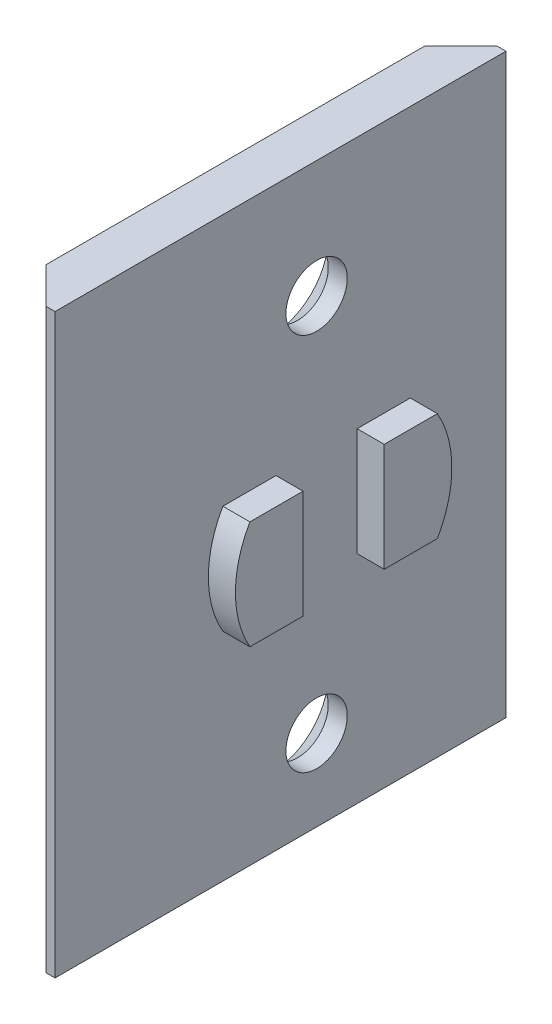
SolidWorks part; units mm, degrees
material "Сталь"
ref_plane "Спереди" through (0, 0, 0) normal (0, 0, 1) x (1, 0, 0)
ref_plane "Сверху" through (0, 0, 0) normal (0, 1, 0) x (1, 0, 0)
ref_plane "Справа" through (0, 0, 0) normal (1, 0, 0) x (0, 0, -1)
sketch "Эскиз1" plane through (0, 0, 0) normal (1, 0, 0) x (0, 0, -1)
  line L1 (-12.5, -16) -> (12.5, -16)
  line L2 (-12.5, -16) -> (-12.5, 16)
  line L3 (-12.5, 16) -> (12.5, 16)
  line L4 (12.5, -16) -> (12.5, 16)
  line L5 (-12.5, -16) -> (12.5, 16) construction
  line L6 (-12.5, 16) -> (12.5, -16) construction
  point P0 (0, 0)
  dimension "D1" = 25
  dimension "D2" = 32
extrude "Бобышка-Вытянуть1" add sketch "Эскиз1" along normal blind 2.5
chamfer "Фаска1" distance 2 angle 45 2 edges at (0, 0, 12.5) (0, 0, -12.5)
sketch "Эскиз2" plane through (0, 0, 0) normal (1, 0, 0) x (0, 0, -1)
  point P0 (2, 9.5)
  point P1 (2, -11.5)
hole_wizard "Зенковка для  винта с плоской головкой M31" positions "Трехмерный эскиз1" profile "Эскиз3" countersink size "M3" standard "Ansi Metric" end condition through all
sketch3d "Трехмерный эскиз1"
  point P0 (0, -11.5, -2)
  point P3 (0, 9.5, -2)
sketch "Эскиз3" plane through (0, -11.5, -2) normal (0, 1, 0) x (0, 0, 1)
  line L0 (0, 0) -> (0, 2.5)
  line L1 (0, 2.5) -> (1.7, 2.5)
  line L2 (1.7, 2.5) -> (1.7, 1.45)
  line L3 (1.7, 1.45) -> (3.15, 0)
  line L5 (3.15, 0) -> (0, 0)
  line L6 (-1.7, 1.45) -> (-3.15, 0) construction
  line L11 (0, -6.35) -> (0, 107.95) construction
  dimension "Диаметр сквозного отверстия" = 3.4
  dimension "Глубина сквозного отверстия" = 2.5
  dimension "Диаметр передней зенковки" = 6.3
  dimension "Угол передней зенковки" = 90
sketch "Эскиз4" plane through (2.5, 0, 0) normal (1, 0, 0) x (0, 0, -1)
  line L1 (-0.25, -3.681) -> (4.25, -3.681)
  line L2 (-0.25, -3.681) -> (-0.25, 1.681)
  line L3 (-0.25, 1.681) -> (4.25, 1.681)
  line L4 (4.25, -3.681) -> (4.25, 1.681)
  line L5 (-0.25, -3.681) -> (4.25, 1.681) construction
  line L6 (-0.25, 1.681) -> (4.25, -3.681) construction
  circle A0 centre (2, -1) radius 6
  circle A1 centre (2, -1) radius 3.5
  dimension "D1" = 12
  dimension "D2" = 7
extrude "Бобышка-Вытянуть2" add sketch "Эскиз4" along normal blind 1.5 contours A0 A1 | L2 A1 | L4 A1 region at (2.5, -1, 0.7585) region at (2.5, -1, -4.7585) region at (2.5, -1, 3.8303)
sketch "Эскиз5" plane through (4, 0, 0) normal (1, 0, 0) x (0, 0, -1)
  line L0 (4.25, -3.681) -> (4.25, 1.681) construction
  line L1 (-0.25, -9) -> (4.25, -9)
  line L2 (-0.25, -9) -> (-0.25, 7)
  line L3 (-0.25, 7) -> (4.25, 7)
  line L4 (4.25, -9) -> (4.25, 7)
  line L5 (-0.25, -9) -> (4.25, 7) construction
  line L6 (-0.25, 7) -> (4.25, -9) construction
  point P0 (2, -1)
  dimension "D1" = 16
extrude "Вырез-Вытянуть1" cut sketch "Эскиз5" against normal up to surface (1.5 mm away) up to face at (2.5, 0, 0)
sketch "Эскиз6" plane through (4, 0, 0) normal (1, 0, 0) x (0, 0, -1)
  line L1 (-3.1962, -4) -> (7.1962, -4)
  line L2 (-3.1962, -4) -> (-3.1962, 2)
  line L3 (-3.1962, 2) -> (7.1962, 2)
  line L4 (7.1962, -4) -> (7.1962, 2)
  line L5 (-3.1962, -4) -> (7.1962, 2) construction
  line L6 (-3.1962, 2) -> (7.1962, -4) construction
  circle A0 centre (2, -1) radius 6
  arc A2 (4.25, -6.5621) -> (4.25, 4.5621) centre (2, -1) ccw construction
  line M1 (4.25, 4.5621) -> (4.25, -6.5621)
  arc M2 (4.25, -6.5621) -> (4.25, 4.5621) centre (2, -1) ccw
  dimension "D1" = 6
extrude "Вырез-Вытянуть2" cut sketch "Эскиз6" against normal up to surface (1.5 mm away) contours A0 L3 M1 | L3 M1 M2 | L1 A0 M1 | L1 M1 M2 region at (4, -5.304, -1.116) region at (4, -4.9511, -5.3386) region at (4, 3.304, -1.116) region at (4, 2.9511, -5.3386) up to face at (2.5, -1, 2.125)
